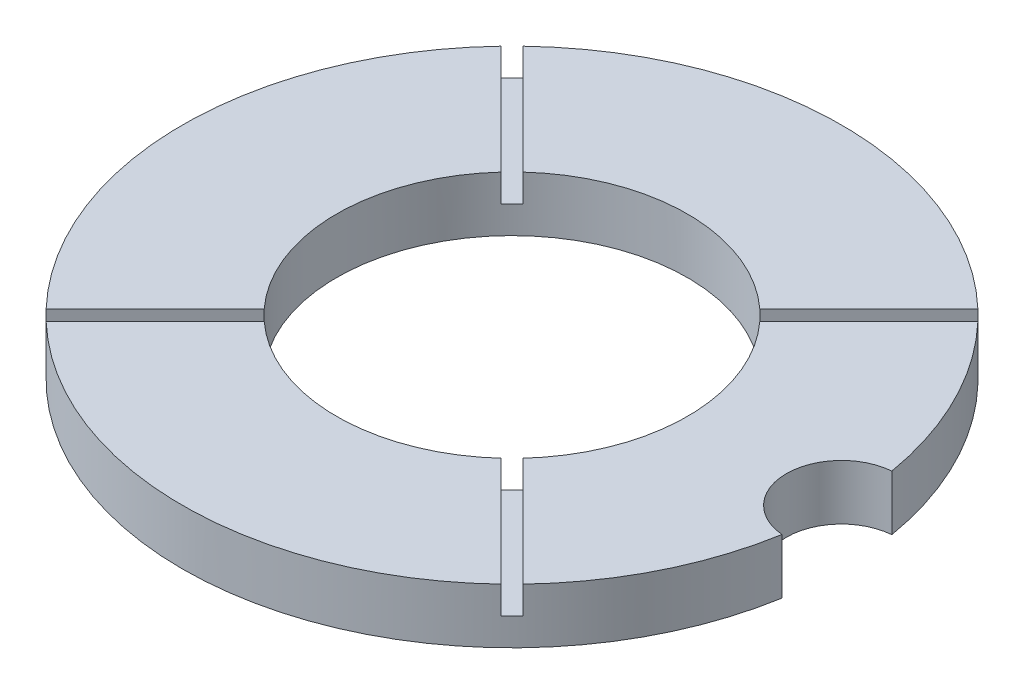
SolidWorks part; units mm, degrees
note: The reader was unsure of these and kept them because the rebuilt part matched: shared geometry of "Sketch1<10>".
ref_plane "Front Plane" through (0, 0, 0) normal (0, 0, 1) x (1, 0, 0)
ref_plane "Top Plane" through (0, 0, 0) normal (0, 1, 0) x (1, 0, 0)
ref_plane "Right Plane" through (0, 0, 0) normal (1, 0, 0) x (0, 0, -1)
sketch "Sketch1" plane through (0, 0, 0) normal (0, 1, 0) x (1, 0, 0)
  circle A0 centre (0, 0) radius 40.4114
  circle A1 centre (0, 0) radius 75.9206
  dimension "D1" = 80.8228
  dimension "D2" = 151.8412
extrude "Boss-Extrude1" add sketch "Sketch1" along normal blind 12.7 contours A1
extrude "Cut-Extrude2" cut sketch "Sketch1<10>" along normal through all contours A0
sketch "Sketch1<10>" plane through (0, 0, 0) normal (0, 1, 0) x (1, 0, 0) same geometry as "Sketch1"
sketch "Sketch2" plane through (0, 12.7, 0) normal (0, 1, 0) x (1, 0, 0)
  line L1 (0, 0) -> (75.9206, 0)
  circle A1 centre (0, 0) radius 75.9206 construction
  circle A2 centre (0, 0) radius 75.9206
  circle A3 centre (75.9206, 0) radius 12.7
  circle M4 centre (0, 0) radius 75.9206
  dimension "D1" = 25.4
extrude "Cut-Extrude3" cut sketch "Sketch2" against normal through all contours A3 L1 M4 | L1 A3 M4
sketch "Sketch3" plane through (0, 12.7, 0) normal (0, 1, 0) x (1, 0, 0)
  line L2 (0, 0) -> (-64.4052, 64.4052) construction
  line L7 (-28.18, 25.7015) -> (-25.7015, 28.18)
  line L8 (-28.18, 25.7015) -> (-63.0053, 60.5267)
  line L19 (0, 0) -> (0, 89.3827) construction
  line L20 (-25.7015, 28.18) -> (-60.5267, 63.0053)
  line L21 (-63.0053, 60.5267) -> (-60.5267, 63.0053)
  line L22 (-28.18, 25.7015) -> (-60.5267, 63.0053) construction
  line L23 (-25.7015, 28.18) -> (-63.0053, 60.5267) construction
  line L24 (28.18, 25.7015) -> (63.0053, 60.5267)
  line L25 (25.7015, 28.18) -> (28.18, 25.7015)
  line L26 (25.7015, 28.18) -> (60.5267, 63.0053)
  line L27 (60.5267, 63.0053) -> (63.0053, 60.5267)
  line L28 (25.7015, -28.18) -> (60.5267, -63.0053)
  line L29 (28.18, -25.7015) -> (25.7015, -28.18)
  line L30 (28.18, -25.7015) -> (63.0053, -60.5267)
  line L31 (63.0053, -60.5267) -> (60.5267, -63.0053)
  line L32 (-28.18, -25.7015) -> (-63.0053, -60.5267)
  line L33 (-25.7015, -28.18) -> (-28.18, -25.7015)
  line L34 (-25.7015, -28.18) -> (-60.5267, -63.0053)
  line L35 (-60.5267, -63.0053) -> (-63.0053, -60.5267)
  point P0 (0, 0)
  point P4 (-44.3534, 44.3534)
  point P9 (0, 0)
  point P25 (0, 0)
  point P30 (0, 0)
  point P31 (-4.3236, 4.5408)
  dimension "D1" = 45
  dimension "D2" = 3.5052
  dimension "D3" = 38.1
  dimension "D4" = 4
ref_plane "Plane1" through (0, 6.35, 0) normal (0, 1, 0) x (1, 0, 0)
extrude "Cut-Extrude5" cut sketch "Sketch3" against normal blind 6.35
equation "\"Bodytube_OD\"= 6.17in"
equation "\"Bodytube_ID\"= 5.998in"
equation "\"Motor_OD\"= 4in"
equation "\"Fwd_Tube_Length\"= 38in"
equation "\"Mid_Tube_Length\"= 8in"
equation "\"Aft_Section_Length\"= 40in"
equation "\"Mid_Coupler_Length\"= 13in"
equation "\"Aft_Lower_Length\"= 22in"
equation "\"AB_Coupler_OD_Length\"= 1in"
equation "\"AB_Coupling_Section_Length\"= 0.375in"
equation "\"AB_Coupler_Length\"= \"AB_Coupler_OD_Length\" + \"AB_Coupling_Section_Length\" * 2"
equation "\"Cutout_Angle\"= 80"
equation "\"AB_Paddle_Height\"= 0.375in"
equation "\"AB_Coupler_Num_Screws\"= 6"
equation "\"Num_Cutouts\"= 3"
equation "\"AB_Coupler_OD\"= 6.17in"
equation "\"AB_Coupler_ID\"= 5.75in"
equation "\"AB_Coupler_Surface_Diameter\"= 5.998in"
equation "\"AB_Coupling_Screw_Diameter\"= 0.1065in"
equation "\"AB_Central_Bushing_Length\"= .75in"
equation "\"Lead_Screw_Dist\"= 2.25in"
equation "\"Lead_Screw_Diam\"= (27/64)*1in"
equation "\"Lead_Screw_Length\"= (\"Mid_Coupler_Length\" + 2*0.375in + 2*0.5in)"
equation "\"Paddle_Pin_Offset\"= .25in"
equation "\"Paddle_Pin_Radius\"= 2.25in"
equation "\"Paddle_Gear_OD\"= 3.2in"
equation "\"Fwd_BKHD_From_Top\"= 18in"
equation "\"D2@Sketch1\" = \"Bodytube_ID\" - 0.02"
equation "\"D1@Sketch1\" = 3.162 + 0.02"
equation "\"Fin_Thickness\"= .118in"
equation "\"Guiderail_Cutout_Diameter\"= 1.5in"
equation "\"D1@Sketch2\" = 1"
equation "\"D2@Sketch3\"= \"Fin_Thickness\" + 0.02"
